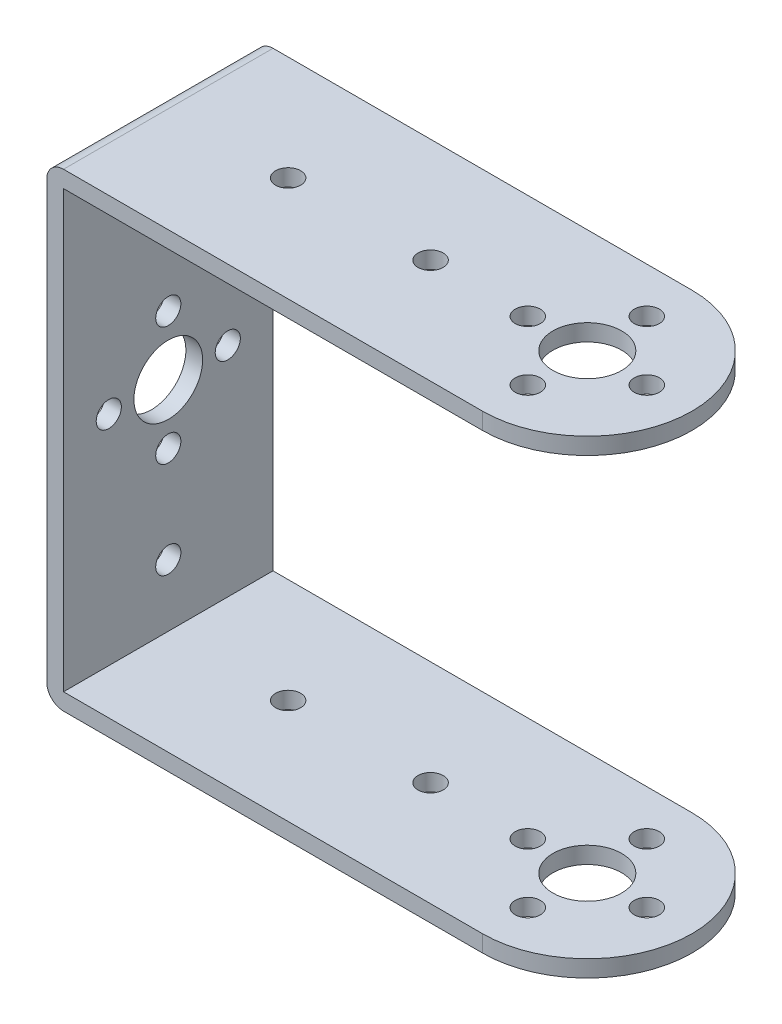
SolidWorks part; units mm, degrees
ref_plane "前视基准面" through (0, 0, 0) normal (0, 0, 1) x (1, 0, 0)
ref_plane "上视基准面" through (0, 0, 0) normal (0, 1, 0) x (1, 0, 0)
ref_plane "右视基准面" through (0, 0, 0) normal (1, 0, 0) x (0, 0, -1)
sketch "草图1" plane through (0, 0, 0) normal (0, 1, 0) x (1, 0, 0)
  line L1 (22, -12.5) -> (-22, -12.5)
  line L2 (22, -12.5) -> (22, 12.5)
  line L3 (22, 12.5) -> (-22, 12.5)
  line L4 (-22, -12.5) -> (-22, 12.5)
  line L5 (22, -12.5) -> (-22, 12.5) construction
  line L6 (22, 12.5) -> (-22, -12.5) construction
  point P0 (0, 0)
  dimension "D1" = 44
  dimension "D2" = 25
extrude "凸台-拉伸1" add sketch "草图1" against normal blind 2
ref_plane "基准面1" through (0, -28, 0) normal (0, 1, 0) x (1, 0, 0)
fillet "圆角1" 2 edges at (22, -1, 12.5) (22, -1, -12.5) type full round first side face at (0, -1, 12.5) second side face at (0, -1, -12.5) middle face at (22, -1, 0)
sketch "草图3" plane through (0, 0, 0) normal (0, 1, 0) x (1, 0, 0)
  line L0 (-29.3505, 0) -> (38.6848, 0) construction
  line L1 (9.5, 7.9337) -> (9.5, -10.0875) construction
  circle A0 centre (9.5, 0) radius 4.1
  arc A1 (9.5, -12.5) -> (9.5, 12.5) centre (9.5, 0) ccw construction
  circle A2 centre (2.4, 0) radius 1.5
  circle A3 centre (9.5, 7.1) radius 1.5
  circle A4 centre (16.6, 0) radius 1.5
  circle A5 centre (9.5, -7.1) radius 1.5
  circle A6 centre (-9.2, 0) radius 1.5
  point P21 (9.5, 0)
  dimension "D1" = 8.2
  dimension "D2" = 8.4
  dimension "D3" = 3
  dimension "D4" = 1.5
  dimension "D6" = 3
  dimension "D7" = 8.6
  dimension "D5" = 4
extrude "切除-拉伸2" cut sketch "草图3" against normal up to next
sketch "草图4" plane through (-22, 0, 0) normal (-1, 0, 0) x (0, 0, 1)
  line L4 (12.5, 0) -> (-12.5, 0)
  line L5 (-12.5, 0) -> (-12.5, -2)
  line L6 (-12.5, -2) -> (12.5, -2)
  line L7 (12.5, -2) -> (12.5, 0)
  line L8 (12.5, 0) -> (-12.5, 0)
  line L9 (-12.5, 0) -> (-12.5, -2)
  line L10 (-12.5, -2) -> (12.5, -2)
  line L11 (12.5, -2) -> (12.5, 0)
  dimension "D1" = 0
extrude "凸台-拉伸2" add sketch "草图4" along normal blind 20.5
sketch "草图5" plane through (0, 0, 0) normal (0, 1, 0) x (1, 0, 0)
  line L0 (-45.3843, 0) -> (32.3512, 0) construction
  circle A0 centre (-26.2, 0) radius 1.5
  circle A1 centre (-9.2, 0) radius 1.5 construction
  dimension "D1" = 3
  dimension "D2" = 14
extrude "切除-拉伸3" cut sketch "草图5" against normal up to next
sketch "草图6" plane through (0, 0, 0) normal (0, 1, 0) x (1, 0, 0)
  line L0 (-42.5, -12.5) -> (9.5, -12.5) construction
  line L1 (-42.5, 12.5) -> (-40.5, 12.5)
  line L2 (-42.5, 12.5) -> (-42.5, -12.5)
  line L3 (-42.5, -12.5) -> (-40.5, -12.5)
  line L4 (-40.5, 12.5) -> (-40.5, -12.5)
  dimension "D1" = 2
extrude "凸台-拉伸3" add sketch "草图6" against normal blind 56
sketch "草图7" plane through (-42.5, 0, 0) normal (-1, 0, 0) x (0, 0, 1)
  line L0 (0, 2.5995) -> (0, -59.7231) construction
  line L1 (-23.5957, -28) -> (24.7942, -28) construction
  line L2 (-12.5, 0) -> (-12.5, -56) construction
  circle A0 centre (0, -28) radius 4.1
  circle A1 centre (-7.1, -28) radius 1.5
  circle A2 centre (0, -20.9) radius 1.5
  circle A3 centre (7.1, -28) radius 1.5
  circle A4 centre (0, -35.1) radius 1.5
  circle A5 centre (0, -9.4) radius 1.5
  circle A6 centre (0, -46.6) radius 1.5
  point P9 (-12.5, -28)
  point P21 (0, -28)
  dimension "D1" = 8.2
  dimension "D2" = 3
  dimension "D3" = 1.5
  dimension "D5" = 3
  dimension "D6" = 8.5
  dimension "D4" = 4
extrude "切除-拉伸4" cut sketch "草图7" against normal up to next
mirror "镜向1" about plane through (0, -28, 0) normal (0, 1, 0) of bodies 116
fillet "圆角2" radius 2 2 edges at (-42.5, -56, 0) (-42.5, 0, 0)
